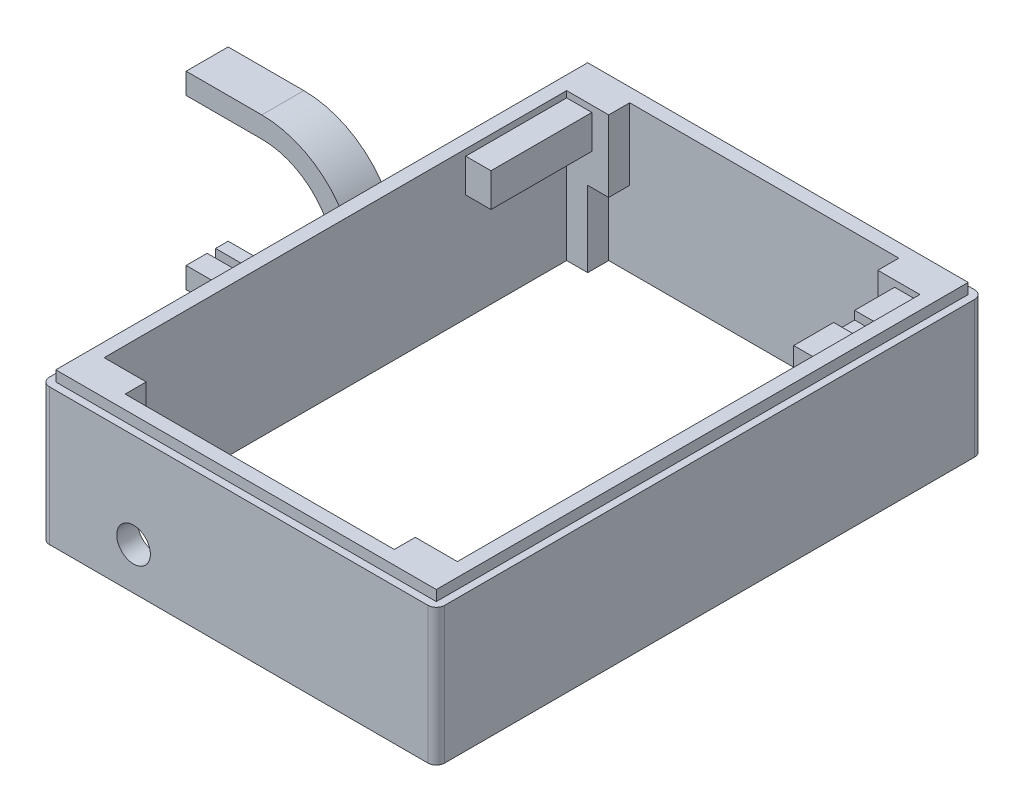
SolidWorks part; units mm, degrees
ref_plane "Front Plane" through (0, 0, 0) normal (0, 0, 1) x (1, 0, 0)
ref_plane "Top Plane" through (0, 0, 0) normal (0, 1, 0) x (1, 0, 0)
ref_plane "Right Plane" through (0, 0, 0) normal (1, 0, 0) x (0, 0, -1)
sketch "Sketch1" plane through (0, 0, 0) normal (0, 1, 0) x (1, 0, 0)
  line L0 (79, 125) -> (79, 120)
  line L1 (0, 0) -> (94, 0)
  line L2 (0, 0) -> (0, 130)
  line L3 (0, 130) -> (94, 130)
  line L4 (94, 0) -> (94, 130)
  line L5 (79, 120) -> (89, 120)
  line L6 (89, 120) -> (89, 10)
  line L7 (89, 10) -> (79, 10)
  line L8 (79, 10) -> (79, 5)
  line L9 (79, 5) -> (15, 5)
  line L10 (15, 5) -> (15, 10)
  line L11 (15, 10) -> (5, 10)
  line L12 (5, 10) -> (5, 120)
  line L13 (5, 120) -> (15, 120)
  line L14 (15, 120) -> (15, 125)
  line L15 (15, 125) -> (79, 125)
  point P20 (79, 122.5)
  point P21 (15, 122.5)
  dimension "D1" = 130
  dimension "D2" = 94
  dimension "D3" = 5
  dimension "D4" = 5
  dimension "D5" = 5
  dimension "D6" = 5
  dimension "D7" = 10
  dimension "D8" = 5
  dimension "D9" = 10
  dimension "D11" = 5
extrude "Boss-Extrude1" add sketch "Sketch1" along normal blind 35
sketch "Sketch3" plane through (5, 0, 0) normal (1, 0, 0) x (0, 0, -1)
  line L0 (120, 35) -> (10, 35) construction
  line L1 (120, 33.5) -> (96, 33.5)
  line L2 (120, 33.5) -> (120, 25.5)
  line L3 (120, 25.5) -> (96, 25.5)
  line L4 (96, 33.5) -> (96, 25.5)
  line L5 (120, 35) -> (120, 0) construction
  dimension "D1" = 24
  dimension "D2" = 8
  dimension "D3" = 1.5
extrude "Boss-Extrude2" add sketch "Sketch3" along normal blind 6
ref_plane "Plane1" through (47, 0, 0) normal (-1, 0, 0) x (0, 0, 1)
mirror "Mirror3" about plane through (47, 0, 0) normal (-1, 0, 0) of "Boss-Extrude2"
sketch "Sketch4" plane through (0, 33.5, 0) normal (0, 1, 0) x (1, 0, 0)
  line L0 (83, 120) -> (83, 96) construction
  line L1 (83, 110.5) -> (89, 110.5)
  line L2 (83, 110.5) -> (83, 105.5)
  line L3 (83, 105.5) -> (89, 105.5)
  line L4 (89, 110.5) -> (89, 105.5)
  line L5 (89, 120) -> (89, 96) construction
  point P4 (83, 108)
  point P7 (83, 108)
  dimension "D1" = 5
extrude "Cut-Extrude1" cut sketch "Sketch4" against normal blind 2
sketch "Sketch5" plane through (0, 0, 0) normal (0, -1, 0) x (1, 0, 0)
  line L0 (79, -120) -> (79, -125) construction
  line L1 (84, -125) -> (79, -125)
  line L2 (84, -125) -> (84, -120)
  line L3 (84, -120) -> (79, -120)
  line L4 (79, -125) -> (79, -120)
  line L5 (89, -120) -> (79, -120) construction
  line L6 (79, -125) -> (15, -125) construction
  dimension "D1" = 5
extrude "Cut-Extrude2" cut sketch "Sketch5" against normal blind 18
pattern_linear "LPattern1" count 2 spacing 69 along (-1, 0, 0) count 2 spacing 115 along (0, 0, 1) of "Cut-Extrude2"
fillet "Fillet1" radius 2 4 edges at (0, 17.5, 0) (94, 17.5, 0) (94, 17.5, -130) (0, 17.5, -130)
sketch "Sketch6" plane through (0, 0, 0) normal (0, 0, 1) x (1, 0, 0)
  line L0 (2, 0) -> (92, 0) construction
  line L1 (2, 35) -> (2, 0) construction
  circle A0 centre (22, 10) radius 4
  dimension "D1" = 8
  dimension "D2" = 10
  dimension "D3" = 20
extrude "Cut-Extrude3" cut sketch "Sketch6" against normal blind 7
sketch "Sketch7" plane through (0, 35, 0) normal (0, 1, 0) x (1, 0, 0)
  line L0 (92, 130) -> (2, 130) construction
  line L5 (1.75, 128.25) -> (92.25, 128.25)
  line L6 (1.75, 128.25) -> (1.75, 1.75)
  line L7 (1.75, 1.75) -> (92.25, 1.75)
  line L8 (92.25, 128.25) -> (92.25, 1.75)
  line L9 (0, 128) -> (0, 2) construction
  line L10 (2, 0) -> (92, 0) construction
  line L11 (94, 2) -> (94, 128) construction
  line L12 (94, 2) -> (94, 128)
  line L13 (2, 0) -> (92, 0)
  line L14 (0, 128) -> (0, 2)
  line L15 (92, 130) -> (2, 130)
  arc A0 (94, 128) -> (92, 130) centre (92, 128) ccw construction
  arc A1 (92, 0) -> (94, 2) centre (92, 2) ccw construction
  arc A2 (0, 2) -> (2, 0) centre (2, 2) ccw construction
  arc A3 (2, 130) -> (0, 128) centre (2, 128) ccw construction
  arc A4 (94, 128) -> (92, 130) centre (92, 128) ccw
  arc A5 (92, 0) -> (94, 2) centre (92, 2) ccw
  arc A6 (0, 2) -> (2, 0) centre (2, 2) ccw
  arc A7 (2, 130) -> (0, 128) centre (2, 128) ccw
  dimension "D1" = 1.75
  dimension "D2" = 1.75
  dimension "D3" = 1.75
  dimension "D4" = 1.75
extrude "Cut-Extrude4" cut sketch "Sketch7" against normal blind 2.5
ref_plane "Plane7" through (0, 0, -80) normal (0, 0, 1) x (1, 0, 0)
ref_axis "Axis1" through (0, 38.5, -80) along (0, -1, 0)
ref_plane "Plane12" through (0, 16.25, 0) normal (0, -1, 0) x (-1, 0, 0)
ref_point "Point1"
sketch "Sketch14" plane through (0, 0, 0) normal (-1, 0, 0) x (0, 0, 1)
  line L5 (-84, 21.25) -> (-76, 21.25)
  line L6 (-84, 21.25) -> (-84, 11.25)
  line L7 (-84, 11.25) -> (-76, 11.25)
  line L8 (-76, 21.25) -> (-76, 11.25)
  line L9 (-84, 21.25) -> (-76, 11.25) construction
  line L10 (-84, 11.25) -> (-76, 21.25) construction
  point P0 (-80, 16.25)
  point P5 (0, 0)
  dimension "D1" = 8
  dimension "D2" = 10
extrude "Boss-Extrude6" add sketch "Sketch14" along normal blind 5
sketch "Sketch17" plane through (0, 0, -80) normal (0, 0, 1) x (1, 0, 0)
  line L0 (0, 38.5) -> (0, -11) construction
  line L1 (-22.5, -6.25) -> (-22.5, 38.75) construction
  line L2 (-22.5, 38.75) -> (-40.5, 38.75)
  line L3 (-40.5, 38.75) -> (-40.5, 33.75)
  line L4 (-40.5, 33.75) -> (-22.5, 33.75)
  line L5 (-22.5, -1.25) -> (-40.5, -1.25)
  line L6 (-40.5, -1.25) -> (-40.5, -6.25)
  line L7 (-40.5, -6.25) -> (-22.5, -6.25)
  arc A0 (-22.5, -1.25) -> (-22.5, 33.75) centre (-22.5, 16.25) ccw
  arc A1 (-22.5, -6.25) -> (-22.5, 38.75) centre (-22.5, 16.25) ccw
  circle A3 centre (-22.5, 16.25) radius 17.5 construction
  circle A4 centre (-22.5, 16.25) radius 22.5 construction
  point P1 (-0.9831, 20.3284)
  point P14 (0, 0)
  point P16 (0, 0)
  point P17 (0, 0)
  point P18 (0, 0)
  point P19 (0, 0)
  point P20 (-5.7647, 18.8665)
  dimension "D1" = 35
  dimension "D3" = 22.5
  dimension "D4" = 18
  dimension "D2" = 5
extrude "Boss-Extrude9" add sketch "Sketch17" along normal mid plane 10 separate body
sketch "Sketch18" plane through (0, 33.75, 0) normal (0, -1, 0) x (1, 0, 0)
  line L0 (-40.5, -75) -> (-40.5, -85) construction
  line L1 (-22.5, -82) -> (-40.5, -82)
  line L2 (-22.5, -82) -> (-22.5, -78)
  line L3 (-22.5, -78) -> (-24.5, -78)
  line L4 (-40.5, -82) -> (-40.5, -80)
  line L5 (-22.5, -75) -> (-22.5, -85) construction
  line L6 (-40.5, -85) -> (-22.5, -85) construction
  line L7 (-24.5, -78) -> (-24.5, -80)
  line L12 (-24.5, -80) -> (-40.5, -80)
  point P13 (-24.5, -79)
  dimension "D2" = 3
  dimension "D3" = 2
  dimension "D4" = 2
extrude "Cut-Extrude6" cut sketch "Sketch18" against normal blind 2
mirror "Mirror4" about plane through (0, 16.25, 0) normal (0, -1, 0) of "Cut-Extrude6"
